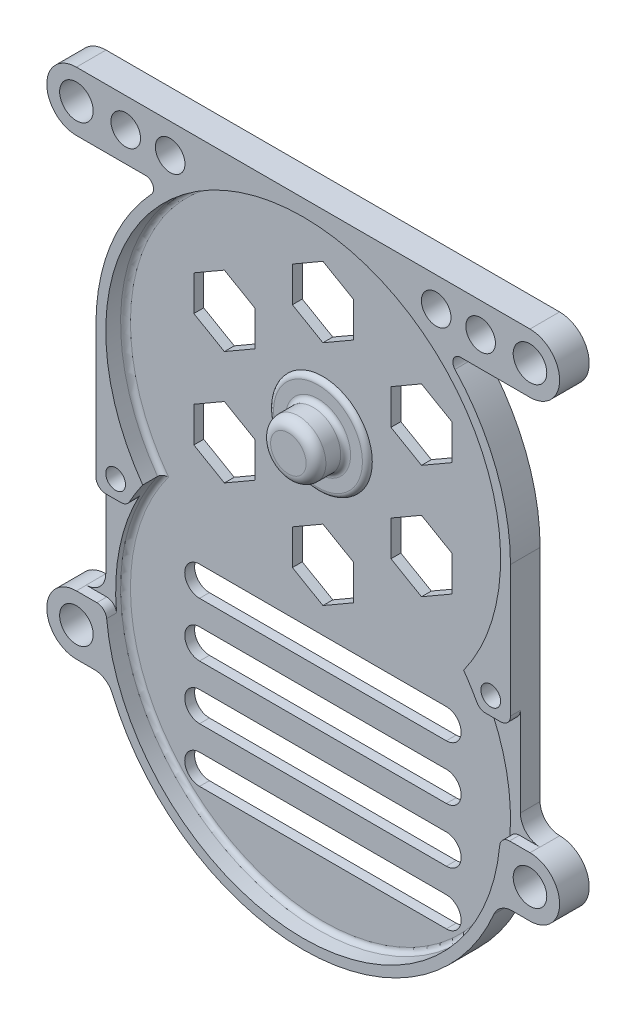
SolidWorks part; units mm, degrees
ref_plane "Ebene vorne" through (0, 0, 0) normal (0, 0, 1) x (1, 0, 0)
ref_plane "Ebene oben" through (0, 0, 0) normal (0, 1, 0) x (1, 0, 0)
ref_plane "Ebene rechts" through (0, 0, 0) normal (1, 0, 0) x (0, 0, -1)
sketch "groundplate" plane through (0, 0, 0) normal (0, 0, 1) x (1, 0, 0)
  line L0 (1, 5.6926) -> (1, -17.6074) construction
  line L1 (22, 5.6926) -> (22, -17.6074) construction
  line L2 (-20, 5.6926) -> (-20, -17.6074) construction
  line L3 (22, 5.6926) -> (22, -17.6074)
  line L4 (-20, 5.6926) -> (-20, -17.6074)
  arc A0 (-20, 5.6926) -> (22, 5.6926) centre (1, 5.6926) cw
  arc A1 (-20, -17.6074) -> (22, -17.6074) centre (1, -17.6074) ccw
  dimension "D1" = 23.3
  dimension "D2" = 42
  dimension "D3" = 23.3
extrude "body" add sketch "groundplate" along normal blind 3 contours L4 A1 A0 region at (1, -5.9574, 0)
sketch "main-box" plane through (0, 0, 3) normal (0, 0, 1) x (1, 0, 0)
  line L0 (-20, 5.6926) -> (22, 5.6926) construction
  line L1 (-20, -17.6074) -> (22, -17.6074) construction
  arc A0 (-20, -17.6074) -> (22, -17.6074) centre (1, -17.6074) ccw construction
  circle A1 centre (1, 5.6926) radius 20
  circle A2 centre (1, -17.6074) radius 20
  dimension "D1" = 40
extrude "box" cut sketch "main-box" against normal blind 2 contours A1 A2 | A2 A1 | A1 A2 region at (1, 10.7505, 3) region at (1, -5.9574, 3) region at (1, -22.6654, 3)
sketch "rack-channel" plane through (0, 0, 3) normal (0, 0, 1) x (1, 0, 0)
  line L0 (-20, -17.6074) -> (22, -17.6074) construction
  line L1 (-20, 5.6926) -> (-20, -17.6074) construction
  line L2 (-20, -8.6074) -> (22, -8.6074)
  line L3 (-20, -8.6074) -> (-20, -18.6074)
  line L4 (-20, -18.6074) -> (22, -18.6074)
  line L5 (22, -8.6074) -> (22, -18.6074)
  dimension "D1" = 1
  dimension "D2" = 10
extrude "rack-ch" cut sketch "rack-channel" against normal blind 1
ref_axis "Achse1" through (1, 5.6926, 1) along (0, 0, 1)
ref_axis "Achse2" through (1, -17.6074, 1) along (0, 0, 1)
fillet "Verrundung1" radius 1 2 edges at (22, -8.6074, 2.5) (-20, -8.6074, 2.5)
sketch "wings-" plane through (0, 0, 3) normal (0, 0, 1) x (1, 0, 0)
  line L0 (-36.7847, -18.6074) -> (40.263, -18.6074) construction
  line L1 (-36.7847, -24.6074) -> (40.263, -24.6074) construction
  line L2 (-19.9762, -18.6074) -> (-21.9762, -18.6074)
  line L3 (-18.799, -24.6074) -> (-21.9762, -24.6074)
  line L4 (-21.9762, -18.6074) -> (-21.9762, -24.6074) construction
  line L5 (-19, -17.6074) -> (21, -17.6074) construction
  line L6 (21.9762, -18.6074) -> (23.9762, -18.6074)
  line L7 (23.9762, -18.6074) -> (23.9762, -24.6074) construction
  line L8 (20.799, -24.6074) -> (23.9762, -24.6074)
  arc A0 (-21.9762, -18.6074) -> (-21.9762, -24.6074) centre (-21.9762, -21.6074) ccw
  arc A1 (-15.2566, -5.9574) -> (17.2566, -5.9574) centre (1, -17.6074) ccw construction
  arc A2 (-16.8606, -8.6074) -> (-18.975, -18.6074) centre (1, -17.6074) ccw construction
  arc A3 (-19.9762, -18.6074) -> (-18.799, -24.6074) centre (1, -17.6074) ccw
  arc A4 (-19.9762, -18.6074) -> (21.9762, -18.6074) centre (1, -17.6074) ccw construction
  arc A5 (23.9762, -18.6074) -> (23.9762, -24.6074) centre (23.9762, -21.6074) cw
  arc A6 (21.9762, -18.6074) -> (20.799, -24.6074) centre (1, -17.6074) cw
  dimension "D3" = 2
  dimension "D1" = 6
  dimension "D2" = 2
extrude "wings" add sketch "wings-" against normal blind 3
sketch "Skizze6" plane through (0, 0, 3) normal (0, 0, 1) x (1, 0, 0)
  circle A0 centre (-21.9762, -21.6074) radius 1.7
  circle A1 centre (23.9762, -21.6074) radius 1.7
  dimension "D1" = 3.4
extrude "wing-hole" cut sketch "Skizze6" against normal through all
sketch "baseaxis" plane through (0, 0, 1) normal (0, 0, 1) x (1, 0, 0)
  circle A0 centre (1, 5.6926) radius 5
  dimension "D1" = 10
extrude "base-axis" add sketch "baseaxis" along normal blind 0.5
sketch "gear-axis" plane through (0, 0, 1.5) normal (0, 0, 1) x (1, 0, 0)
  circle A0 centre (1, 5.6926) radius 2.8
  dimension "D1" = 5.6
extrude "top-axis" add sketch "gear-axis" along normal blind 3
fillet "Verrundung2" radius 1 1 edges at (3.8, 5.6926, 4.5)
fillet "Verrundung3" radius 0.5 2 edges at (6, 5.6926, 1.5) (3.8, 5.6926, 1.5)
fillet "Verrundung4" radius 0.5 1 edges at (1, 25.6926, 1)
fillet "Verrundung5" radius 0.5 1 edges at (1, -37.6074, 1)
fillet "Verrundung6" radius 1 4 edges at (-18.975, -18.6074, 2.5) (20.975, -18.6074, 2.5) (-16.8606, -8.6074, 2.5) (18.8606, -8.6074, 2.5)
sketch "Skizze12" plane through (0, 0, 1) normal (0, 0, 1) x (1, 0, 0)
  line L0 (1, 26.6926) -> (1, -38.6074) construction
  line L2 (1, 13.6494) -> (4.0934, 15.4354)
  line L3 (4.0934, 15.4354) -> (4.0934, 19.0073)
  line L4 (4.0934, 19.0073) -> (1, 20.7933)
  line L5 (1, 20.7933) -> (-2.0934, 19.0073)
  line L6 (-2.0934, 19.0073) -> (-2.0934, 15.4354)
  line L7 (-2.0934, 15.4354) -> (1, 13.6494)
  arc A1 (-18.799, -24.6074) -> (20.799, -24.6074) centre (1, -17.6074) ccw construction
  circle A2 centre (1, 17.2213) radius 3.0934 construction
extrude "Schnitt-Linear austragen2" cut sketch "Skizze12" against normal through all both and the other way through all
pattern_circular "Kreismuster1" count 6 over 360 about axis through (1, 5.6926, 1) along (0, 0, 1) of "Schnitt-Linear austragen2"
sketch "Skizze14" plane through (0, 0, 1) normal (0, 0, 1) x (1, 0, 0)
  line L0 (1, 26.6926) -> (1, -38.6074) construction
  line L1 (-11.5, -13.524) -> (13.5, -13.524) construction
  line L2 (-11.5, -12.024) -> (13.5, -12.024)
  line L3 (-11.5, -15.024) -> (13.5, -15.024)
  arc A1 (-18.799, -24.6074) -> (20.799, -24.6074) centre (1, -17.6074) ccw construction
  arc A2 (-11.5, -12.024) -> (-11.5, -15.024) centre (-11.5, -13.524) ccw
  arc A3 (13.5, -15.024) -> (13.5, -12.024) centre (13.5, -13.524) ccw
  point P10 (1, -13.524)
  dimension "D1" = 3
  dimension "D2" = 25
extrude "Schnitt-Linear austragen4" cut sketch "Skizze14" against normal through all
pattern_linear "Lineares Muster1" count 4 spacing 5.5 along (0, -1, 0) of "Schnitt-Linear austragen4"
sketch "Skizze15" plane through (0, 0, 3) normal (0, 0, 1) x (1, 0, 0)
  line L0 (-20, 5.6926) -> (22, 5.6926) construction
  line L2 (-20, 5.6926) -> (-20, -7.6074) construction
  line L3 (22, 5.6926) -> (22, -7.6074) construction
  circle A0 centre (-18, -6.8074) radius 1
  circle A1 centre (20, -6.8074) radius 1
  dimension "D1" = 2
  dimension "D4" = 12.5
  dimension "D2" = 12.5
  dimension "D3" = 2
  dimension "D5" = 2
extrude "Schnitt-Linear austragen5" cut sketch "Skizze15" against normal through all
fillet "Verrundung8" radius 2 2 edges at (20.799, -24.6074, 1.5) (-18.799, -24.6074, 1.5)
fillet "Verrundung11" radius 2 2 edges at (21.9762, -18.6074, 1) (-19.9762, -18.6074, 1)
sketch "Skizze16" plane through (0, 0, 3) normal (0, 0, 1) x (1, 0, 0)
  line L0 (-21.9762, -21.6074) -> (-21.9762, 24.3426) construction
  line L1 (23.9762, -21.6074) -> (23.9762, 24.3426) construction
  line L2 (-21.9762, 27.3426) -> (23.9762, 27.3426)
  line L3 (23.9762, 21.3426) -> (15.0028, 21.3426)
  line L4 (-21.9762, 21.3426) -> (-13.0028, 21.3426)
  arc A0 (-21.9762, 21.3426) -> (-21.9762, 27.3426) centre (-21.9762, 24.3426) cw
  arc A1 (23.9762, 21.3426) -> (23.9762, 27.3426) centre (23.9762, 24.3426) ccw
  arc A2 (22, 5.6926) -> (-20, 5.6926) centre (1, 5.6926) ccw construction
  arc A3 (-13.0028, 21.3426) -> (17.8334, 18.2479) centre (1, 5.6926) cw
  circle A4 centre (-21.9762, 24.3426) radius 1.7
  circle A5 centre (23.9762, 24.3426) radius 1.7
  dimension "D3" = 3
  dimension "D4" = 3.4
  dimension "D1" = 45.9524
  dimension "D2" = 45.95
extrude "Aufsatz-Linear austragen2" add sketch "Skizze16" against normal blind 3 contours L4 A3 L3 A1 L2 A0 A5 A4 region at (1, 26.8196, 3)
fillet "Verrundung12" radius 0.8 2 edges at (15.0028, 21.3426, 1.5) (-13.0028, 21.3426, 1.5)
sketch "Skizze17" plane through (0, 0, 3) normal (0, 0, 1) x (1, 0, 0)
  line L0 (-24.9762, 24.3426) -> (26.9762, 24.3426) construction
  arc A0 (-21.9762, 27.3426) -> (-21.9762, 21.3426) centre (-21.9762, 24.3426) ccw construction
  arc A1 (23.9762, 21.3426) -> (23.9762, 27.3426) centre (23.9762, 24.3426) ccw construction
  circle A2 centre (14.4762, 24.3426) radius 1.5
  circle A3 centre (18.9762, 24.3426) radius 1.5
  circle A4 centre (-12.4762, 24.3426) radius 1.5
  circle A5 centre (-16.9762, 24.3426) radius 1.5
  dimension "D1" = 12.5
  dimension "D2" = 3
  dimension "D3" = 3
  dimension "D5" = 12.5
  dimension "D6" = 3
  dimension "D4" = 8
  dimension "D7" = 8
extrude "Schnitt-Linear austragen6" cut sketch "Skizze17" against normal through all
